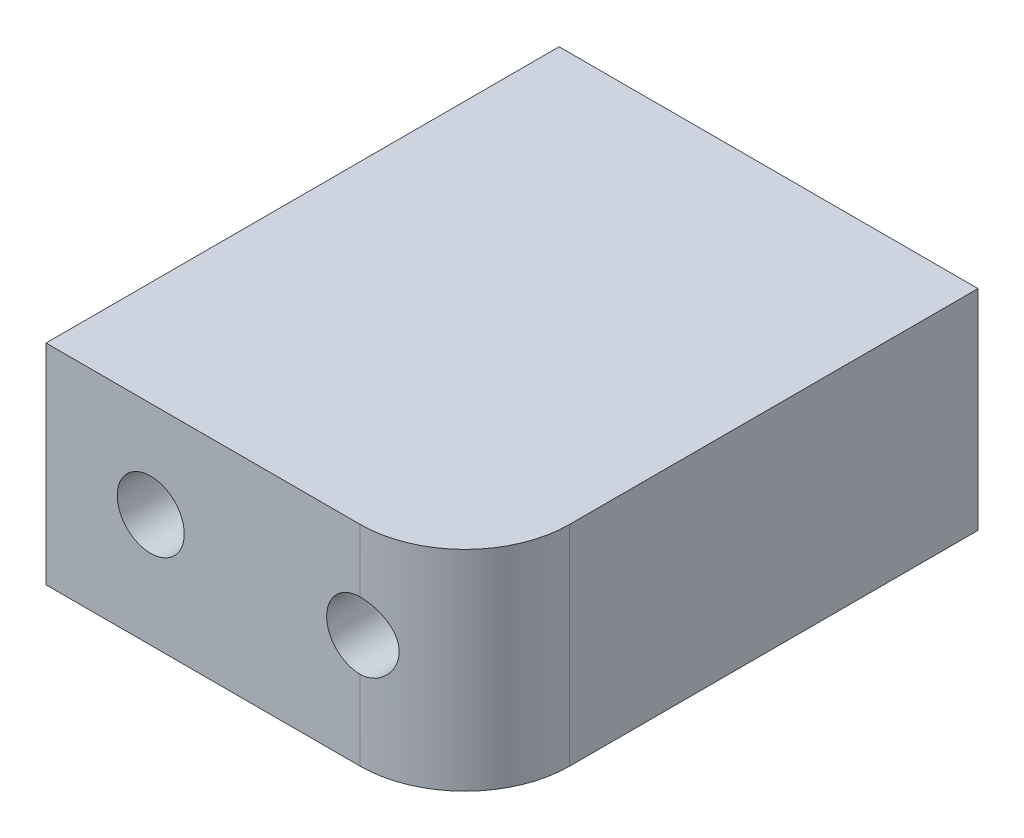
SolidWorks part; units mm, degrees
material "1060 合金"
ref_plane "正面" through (0, 0, 0) normal (0, 0, 1) x (1, 0, 0)
ref_plane "平面" through (0, 0, 0) normal (0, 1, 0) x (1, 0, 0)
ref_plane "右側面" through (0, 0, 0) normal (1, 0, 0) x (0, 0, -1)
sketch "ｽｹｯﾁ1" plane through (0, 0, 0) normal (0, 0, 1) x (1, 0, 0)
  line L0 (0, 5) -> (0, -5) construction
  line L1 (-10, 5) -> (10, 5)
  line L2 (-10, 5) -> (-10, -5)
  line L3 (-10, -5) -> (10, -5)
  line L4 (10, 5) -> (10, -5)
  line L5 (-10, 5) -> (10, -5) construction
  line L6 (-10, -5) -> (10, 5) construction
  line L7 (-5, 0.4) -> (5, 0.4) construction
  circle A0 centre (-5, 0.4) radius 1.6
  circle A1 centre (5, 0.4) radius 1.6
  point P0 (0, 0)
  dimension "D3" = 3.2
  dimension "D1" = 20
  dimension "D2" = 10
  dimension "D4" = 10
  dimension "D5" = 4.6
extrude "ﾎﾞｽ - 押し出し1" add sketch "ｽｹｯﾁ1" along normal blind 24.5
fillet "ﾌｨﾚｯﾄ1" radius 5 1 edges at (10, 0, 24.5)
